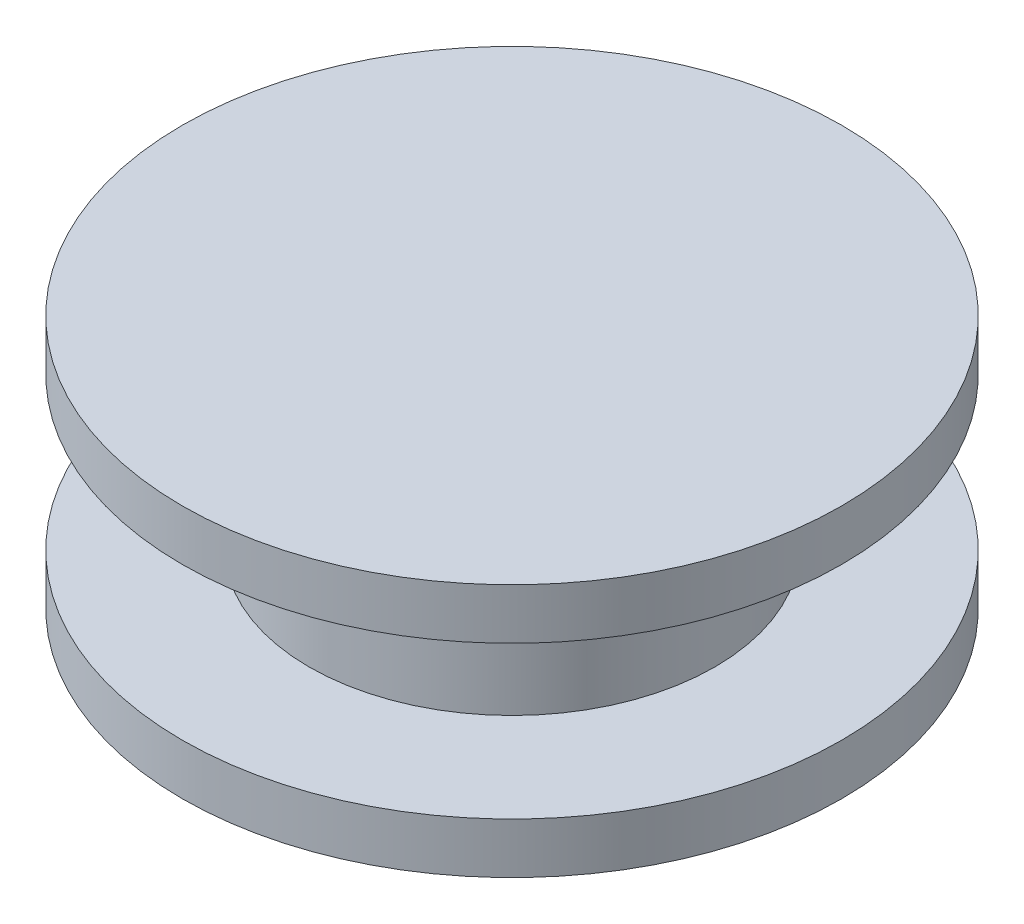
SolidWorks part; units mm, degrees
ref_plane "Front Plane" through (0, 0, 0) normal (0, 0, 1) x (1, 0, 0)
ref_plane "Top Plane" through (0, 0, 0) normal (0, 1, 0) x (1, 0, 0)
ref_plane "Right Plane" through (0, 0, 0) normal (1, 0, 0) x (0, 0, -1)
sketch "Sketch1" plane through (0, 0, 0) normal (0, 1, 0) x (1, 0, 0)
  circle A0 centre (0, 0) radius 20
  dimension "D1" = 40
extrude "Boss-Extrude1" add sketch "Sketch1" along normal mid plane 20
sketch "Sketch2" plane through (0, 10, 0) normal (0, 1, 0) x (1, 0, 0)
  circle A0 centre (0, 0) radius 32.5
  dimension "D1" = 65
extrude "Boss-Extrude2" add sketch "Sketch2" along normal blind 5
extrude "Boss-Extrude3" add sketch "Sketch2<2>" along normal blind 5 from surface starting at face at (0, -10, 20)
sketch "Sketch2<2>" plane through (0, 10, 0) normal (0, 1, 0) x (1, 0, 0) same geometry as "Sketch2"
